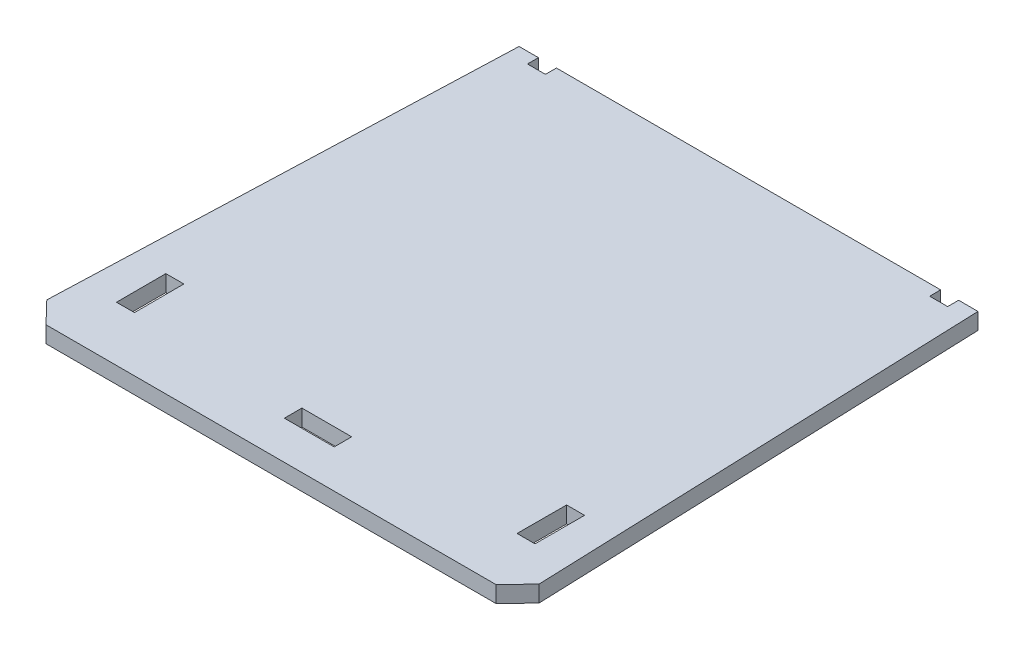
SolidWorks part; units mm, degrees
ref_plane "Front Plane" through (0, 0, 0) normal (0, 0, 1) x (1, 0, 0)
ref_plane "Top Plane" through (0, 0, 0) normal (0, 1, 0) x (1, 0, 0)
ref_plane "Right Plane" through (0, 0, 0) normal (1, 0, 0) x (0, 0, -1)
ref_axis "Axis8" through (88.99, 0, -5.0102) along (-1, 0, 0)
ref_axis "Axis10" through (191.4964, -15.75, 0) along (-0.0871, 0.9962, 0)
ref_axis "Axis11" through (174.996, 0.75, 0) along (0.0871, -0.9962, 0)
ref_axis "Axis12" through (-176.4392, -15.75, 0) along (0.0871, 0.9962, 0)
ref_axis "Axis13" through (-190.0533, 0.75, 0) along (-0.0871, -0.9962, 0)
sketch "Sketch5" plane through (0, 0, 0) normal (0, 0, 1) x (1, 0, 0)
  line L1 (190.1189, 0) -> (191.4309, -15) construction
  line L2 (175.0616, 0) -> (176.3736, -15) construction
  line L3 (-175.0616, 0) -> (-176.3736, -15) construction
  line L4 (-190.1189, 0) -> (-191.4309, -15) construction
  line L5 (191.4964, -15.75) -> (190.0533, 0.75) construction
  line L6 (174.996, 0.75) -> (176.4392, -15.75) construction
  line L7 (-176.4392, -15.75) -> (-174.996, 0.75) construction
  line L8 (-190.0533, 0.75) -> (-191.4964, -15.75) construction
  line L9 (211.4309, 0) -> (-211.4309, 0) construction
  line L10 (55, 0) -> (-55, 0) construction
  line L11 (211.4309, 0) -> (211.4309, -15) construction
  line L12 (211.4309, -15) -> (-211.4309, -15) construction
  line L13 (-211.4309, -15) -> (-211.4309, 0) construction
  line L14 (0, 0) -> (0, -15) construction
  line L15 (0, -55) -> (0, 55) construction
  line L16 (-191.4309, -15) -> (-191.4309, 0)
  line L17 (-175.0616, 0) -> (-175.0616, -15)
  line L18 (-175.0616, 0) -> (-191.4309, 0)
  line L19 (-175.0616, -15) -> (-191.4309, -15)
  line L20 (175.0616, -15) -> (191.4309, -15)
  line L21 (191.4309, -15) -> (191.4309, 0)
  line L22 (175.0616, 0) -> (191.4309, 0)
  line L23 (175.0616, 0) -> (175.0616, -15)
  dimension "D1" = 15
  dimension "D2" = 20
sketch "Sketch1" plane through (0, 0, 0) normal (0, 1, 0) x (1, 0, 0)
  line L0 (-225, 0) -> (225, 0) construction
  line L1 (-225, 0) -> (225, 0) construction
  line L2 (-225, 0) -> (-225, -410.1219) construction
  line L3 (-225, -410.1219) -> (225, -410.1219) construction
  line L4 (225, 0) -> (225, -410.1219) construction
  line L5 (-191.4309, 25.0102) -> (-191.4309, 15.0102)
  line L6 (0, 0) -> (0, -410.1219) construction
  line L7 (-209.8168, 5.0102) -> (209.8168, 5.0102) construction
  line L8 (-225, -410.1219) -> (-209.0853, 25.0102)
  line L9 (88.99, 5.0102) -> (-88.99, 5.0102) construction
  line L10 (209.0853, 25.0102) -> (225, -410.1219)
  line L11 (-191.4309, 15.0102) -> (-175.0616, 15.0102)
  line L12 (225, -410.1219) -> (-225, -410.1219)
  line L13 (-209.0853, 25.0102) -> (209.0853, 25.0102) construction
  line L14 (-175.0616, 15.0102) -> (-175.0616, 25.0102)
  line L15 (191.4309, 15.0102) -> (175.0616, 15.0102)
  line L16 (175.0616, 15.0102) -> (175.0616, 25.0102)
  line L17 (191.4309, 25.0102) -> (191.4309, 15.0102)
  line L18 (-175.0616, 25.0102) -> (175.0616, 25.0102)
  line L19 (209.0853, 25.0102) -> (191.4309, 25.0102)
  line L20 (-210, 0) -> (-225, 0) construction
  line L21 (-209.0853, 25.0102) -> (-191.4309, 25.0102)
  dimension "D1" = 20
  dimension "D2" = 10
  dimension "D3" = 15
extrude "Boss-Extrude1" add sketch "Sketch1" against normal blind 15
ref_axis "Axis1" through (191.4842, -15, -25.0102) along (-0.0021, 0, 1)
ref_axis "Axis2" through (174.9542, 0, 50.3733) along (0.0021, 0, -1)
sketch "Sketch2" plane through (0, -15, 0) normal (0, -1, 0) x (1, 0, 0)
  line L0 (190.6624, 360.2449) -> (190.7585, 315.1669)
  line L1 (190.7585, 315.1669) -> (174.3894, 315.132)
  line L2 (174.3894, 315.132) -> (174.2932, 360.21)
  line L3 (174.2932, 360.21) -> (190.6624, 360.2449)
  line L4 (191.4842, -25.0102) -> (190.556, 410.1219) construction
  line L5 (174.9542, 50.3733) -> (175.4875, -199.6261) construction
  line L8 (175.7194, 360.2131) -> (175.8156, 315.135) construction
  line L9 (190.7585, 315.1669) -> (191.4629, -15.0102) construction
extrude "Cut-Extrude1" cut sketch "Sketch2" against normal through all
mirror "Mirror1" about plane through (0, 0, 0) normal (1, 0, 0) of "Cut-Extrude1"
ref_axis "Axis3" through (-175.1675, 0, -49.6264) along (0.0021, 0, 1)
ref_axis "Axis4" through (174.9542, 0, 50.3733) along (0.0021, 0, -1)
ref_axis "Axis5" through (204.6553, 0, 359.2654) along (1, 0, 0)
ref_axis "Axis6" through (-223.6897, 0, 374.2954) along (1, 0, 0)
ref_axis "Axis7" through (223.1399, 0, 359.2654) along (-1, 0, 0)
sketch "Sketch4" plane through (0, 0, 0) normal (0, 1, 0) x (1, 0, 0)
  line L0 (-22.6879, -359.2654) -> (-22.6879, -375.2449)
  line L1 (-22.6879, -375.2449) -> (22.6879, -375.2449)
  line L2 (22.6879, -375.2449) -> (22.6879, -359.2654)
  line L3 (22.6879, -359.2654) -> (-22.6879, -359.2654)
  line L6 (223.1399, -359.2654) -> (-223.1399, -359.2654) construction
  line L7 (0, -359.2654) -> (0, -375.2449) construction
  line L10 (0, -8.25) -> (0, 8.25) construction
  line L11 (-22.6879, -374.2954) -> (22.6879, -374.2954) construction
  line L12 (-223.6897, -374.2954) -> (223.6897, -374.2954) construction
extrude "Cut-Extrude5" cut sketch "Sketch4" against normal through all
sketch "Sketch6" plane through (0, 0, 0) normal (0, 1, 0) x (1, 0, 0)
  line L0 (0, 0) -> (0, -410.1219) construction
  line L1 (0, 0) -> (0, -410.1219) construction
  line L2 (225, -410.1219) -> (-225, -410.1219) construction
  line L3 (-225, -410.1219) -> (-209.0853, 25.0102) construction
  line L4 (209.0853, 25.0102) -> (225, -410.1219) construction
  line L5 (225, -410.1219) -> (-225, -410.1219) construction
  line L6 (-225, -410.1219) -> (-209.0853, 25.0102) construction
  line L7 (209.0853, 25.0102) -> (225, -410.1219) construction
  line L8 (224.269, -390.1353) -> (205, -410.1219)
  line L9 (205, -410.1219) -> (225, -410.1219)
  line L10 (225, -410.1219) -> (224.269, -390.1353)
  line L11 (-205, -410.1219) -> (-225, -410.1219)
  line L12 (-225, -410.1219) -> (-224.269, -390.1353)
  line L13 (-224.269, -390.1353) -> (-205, -410.1219)
  dimension "D1" = 20
extrude "Cut-Extrude6" cut sketch "Sketch6" against normal through all
